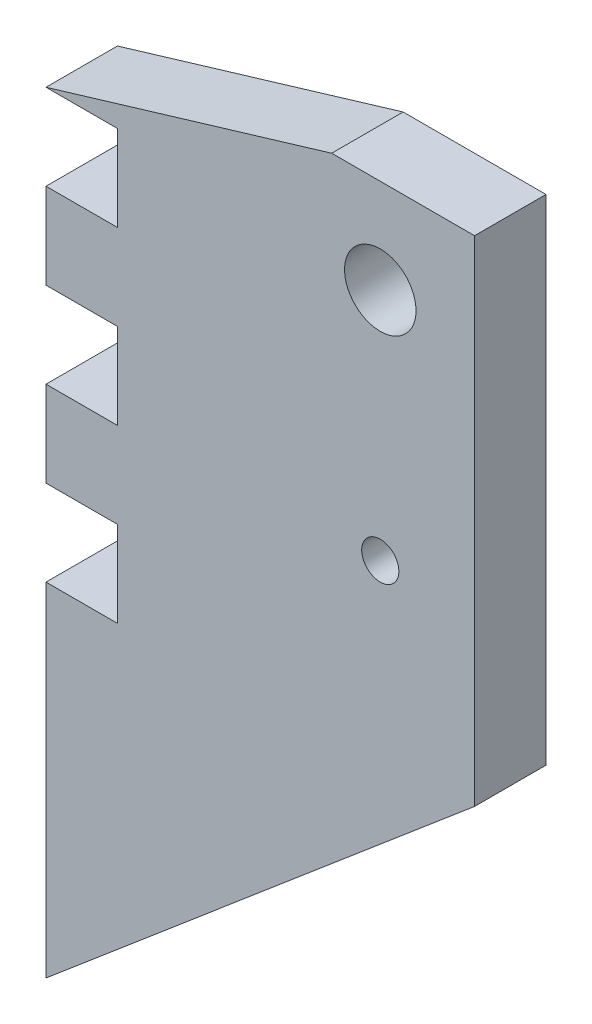
SolidWorks part; units mm, degrees
ref_plane "Front Plane" through (0, 0, 0) normal (0, 0, 1) x (1, 0, 0)
ref_plane "Top Plane" through (0, 0, 0) normal (0, 1, 0) x (1, 0, 0)
ref_plane "Right Plane" through (0, 0, 0) normal (1, 0, 0) x (0, 0, -1)
sketch "Sketch1" plane through (0, 0, 0) normal (0, 0, 1) x (1, 0, 0)
  line L0 (0, 0) -> (-38.1, 0)
  line L1 (0, 0) -> (0, -43.942)
  line L2 (-38.1, 0) -> (-38.1, -7.62)
  line L3 (-38.1, -7.62) -> (-31.75, -7.62)
  line L4 (-31.75, -7.62) -> (-31.75, -15.24)
  line L5 (-31.75, -15.24) -> (-38.1, -15.24)
  line L6 (-38.1, -45.72) -> (-38.1, -76.2)
  line L7 (-38.1, -15.24) -> (-38.1, -22.86)
  line L8 (-38.1, -22.86) -> (-31.75, -22.86)
  line L9 (-31.75, -22.86) -> (-31.75, -30.48)
  line L10 (-31.75, -30.48) -> (-38.1, -30.48)
  line L11 (-38.1, -30.48) -> (-38.1, -38.1)
  line L12 (-38.1, -38.1) -> (-31.75, -38.1)
  line L13 (-31.75, -38.1) -> (-31.75, -45.72)
  line L14 (-31.75, -45.72) -> (-38.1, -45.72)
  line L15 (-38.1, -76.2) -> (0, -43.942)
  circle A0 centre (-8.382, -8.382) radius 3.175
  circle A1 centre (-8.382, -29.21) radius 1.651
  dimension "D9" = 6.35
  dimension "D10" = 3.302
  dimension "D1" = 38.1
  dimension "D2" = 43.942
  dimension "D3" = 7.62
  dimension "D4" = 7.62
  dimension "D5" = 6.35
  dimension "D6" = 6.35
  dimension "D8" = 76.2
  dimension "D11" = 20.828
  dimension "D12" = 8.382
  dimension "D13" = 8.382
  dimension "D14" = 8.382
  dimension "D7" = 3
extrude "Boss-Extrude1" add sketch "Sketch1" along normal blind 6.35 contours L6 L15 L1 L0 L2 L3 L4 L5 L7 L8 L9 L10 L11 L12 L13 L14 A1 A0 region at (-20.0137, -31.3826, 0)
sketch "Sketch2" plane through (0, 0, 0) normal (0, 0, -1) x (-1, 0, 0)
  line L5 (38.1, 0) -> (12.7, 0)
  line L6 (0, 0) -> (38.1, 0) construction
  line L7 (12.7, 0) -> (38.1, -7.62)
  line L8 (38.1, 0) -> (38.1, -7.62) construction
  line L9 (38.1, -7.62) -> (38.1, 0)
  dimension "D1" = 25.4
  dimension "D2" = 7.62
extrude "Cut-Extrude1" cut sketch "Sketch2" against normal blind 8.636
